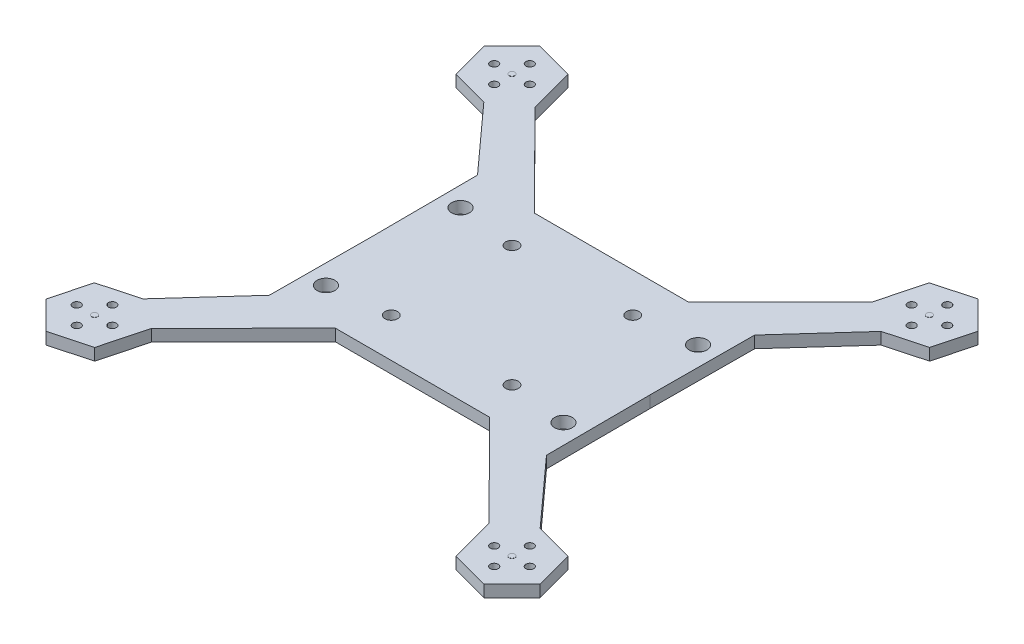
SolidWorks part; units mm, degrees
material "T700G"
ref_plane "Front Plane" through (0, 0, 0) normal (0, 0, 1) x (1, 0, 0)
ref_plane "Top Plane" through (0, 0, 0) normal (0, 1, 0) x (1, 0, 0)
ref_plane "Right Plane" through (0, 0, 0) normal (1, 0, 0) x (0, 0, -1)
sketch "Sketch1" plane through (0, 0, 0) normal (0, 1, 0) x (1, 0, 0)
  line L5 (-35, -35) -> (42.6186, 42.6186) construction
  line L6 (-35, 35) -> (35, -35) construction
  line L9 (0, 0) -> (42.4264, 42.4264) construction
  line L10 (52.7307, 48.2307) -> (52.7307, 57.2307) construction
  line L11 (30, 17) -> (30, 0) construction
  line L12 (0, 0) -> (0, 23.6863) construction
  line L28 (0, 0) -> (-174.2372, 0) construction
  line L41 (31.9599, 25.1581) -> (-25.1581, 25.1581) construction
  line L70 (42.6186, 48.4021) -> (19.4638, 25.1581)
  line L72 (48.2307, 52.7307) -> (57.2307, 52.7307) construction
  line L74 (48.2307, 52.7307) -> (52.7307, 48.2307) construction
  line L75 (55.3003, 62.3949) -> (45.646, 59.7881)
  line L77 (45.646, 59.7881) -> (42.6186, 48.4021)
  line L80 (50.185, 43.0729) -> (59.8153, 45.6732)
  line L83 (59.8153, 45.6732) -> (62.3849, 55.3374)
  line L85 (62.3849, 55.3374) -> (55.3003, 62.3949)
  line L87 (50.185, 43.0729) -> (35, 26.2883)
  line L88 (35, 26.2883) -> (34.873, 0)
  line L89 (34.873, -11.873) -> (34.873, 11.873) construction
  line L90 (-21.8355, 25.1581) -> (21.8355, 25.1581)
  line L94 (35, -26.2883) -> (34.873, 0)
  line L100 (48.2307, -52.7307) -> (52.7307, -48.2307) construction
  line L101 (48.2307, -52.7307) -> (57.2307, -52.7307) construction
  line L102 (52.7307, -48.2307) -> (52.7307, -57.2307) construction
  line L106 (62.3849, -55.3374) -> (55.3003, -62.3949)
  line L111 (59.8153, -45.6732) -> (62.3849, -55.3374)
  line L115 (50.185, -43.0729) -> (59.8153, -45.6732)
  line L116 (45.646, -59.7881) -> (42.6186, -48.4021)
  line L119 (55.3003, -62.3949) -> (45.646, -59.7881)
  line L127 (50.185, -43.0729) -> (35, -26.2883)
  line L128 (35, 26.2883) -> (34.873, 0)
  line L129 (35, -26.2883) -> (34.873, 0)
  line L135 (42.6186, -48.4021) -> (19.4638, -25.1581)
  line L138 (40.4517, 52.7386) -> (49.1512, 44.0725) [skipped]
  line L139 (-21.8355, -25.1581) -> (21.8355, -25.1581)
  line L140 (-48.2307, 52.7307) -> (-52.7307, 48.2307) construction
  line L141 (-48.2307, 52.7307) -> (-57.2307, 52.7307) construction
  line L142 (-52.7307, 48.2307) -> (-52.7307, 57.2307) construction
  line L143 (-62.3849, 55.3374) -> (-55.3003, 62.3949)
  line L144 (-59.8153, 45.6732) -> (-62.3849, 55.3374)
  line L145 (-50.185, 43.0729) -> (-59.8153, 45.6732)
  line L146 (-45.646, 59.7881) -> (-42.6186, 48.4021)
  line L147 (-55.3003, 62.3949) -> (-45.646, 59.7881)
  line L148 (-50.185, 43.0729) -> (-35, 26.2883)
  line L149 (-42.6186, 48.4021) -> (-19.4638, 25.1581)
  line L150 (-35, 26.2883) -> (-34.873, 0)
  line L151 (-35, -26.2883) -> (-34.873, 0)
  line L152 (-50.185, -43.0729) -> (-35, -26.2883)
  line L153 (-42.6186, -48.4021) -> (-19.4638, -25.1581)
  line L154 (-52.7307, -48.2307) -> (-52.7307, -57.2307) construction
  line L155 (-48.2307, -52.7307) -> (-57.2307, -52.7307) construction
  line L156 (-48.2307, -52.7307) -> (-52.7307, -48.2307) construction
  line L157 (-55.3003, -62.3949) -> (-45.646, -59.7881)
  line L158 (-45.646, -59.7881) -> (-42.6186, -48.4021)
  line L159 (-50.185, -43.0729) -> (-59.8153, -45.6732)
  line L160 (-59.8153, -45.6732) -> (-62.3849, -55.3374)
  line L161 (-62.3849, -55.3374) -> (-55.3003, -62.3949)
  circle A0 centre (-15.25, 15.25) radius 1.6
  circle A1 centre (15.25, 15.25) radius 1.6
  circle A2 centre (15.25, -15.25) radius 1.6
  circle A3 centre (-15.25, -15.25) radius 1.6
  circle A18 centre (30, 17) radius 2.25
  circle A19 centre (30, -17) radius 2.25
  circle A20 centre (-30, -17) radius 2.25
  circle A21 centre (-30, 17) radius 2.25
  circle A69 centre (52.7307, 52.7307) radius 8.6603 construction
  circle A70 centre (52.7307, 57.2307) radius 1
  circle A71 centre (52.7307, 48.2307) radius 1
  circle A72 centre (48.2307, 52.7307) radius 1
  circle A73 centre (57.2307, 52.7307) radius 1
  circle A124 centre (52.7307, -52.7307) radius 8.6603 construction
  circle A125 centre (57.2307, -52.7307) radius 1
  circle A126 centre (48.2307, -52.7307) radius 1
  circle A127 centre (52.7307, -48.2307) radius 1
  circle A128 centre (52.7307, -57.2307) radius 1
  circle A129 centre (-52.7307, 52.7307) radius 8.6603 construction
  circle A130 centre (-57.2307, 52.7307) radius 1
  circle A131 centre (-48.2307, 52.7307) radius 1
  circle A132 centre (-52.7307, 48.2307) radius 1
  circle A133 centre (-52.7307, 57.2307) radius 1
  circle A134 centre (-52.7307, -52.7307) radius 8.6603 construction
  circle A135 centre (-52.7307, -57.2307) radius 1
  circle A136 centre (-52.7307, -48.2307) radius 1
  circle A137 centre (-48.2307, -52.7307) radius 1
  circle A138 centre (-57.2307, -52.7307) radius 1
  point P0 (0, 0)
  point P8 (52.7307, 52.7307)
  point P9 (52.7307, 52.7307)
  point P17 (0, 0)
  point P45 (24.8566, 0)
  point P47 (30, 0)
  point P90 (0, 25.1581)
  point P95 (0, -25.1581)
  point P96 (0, 25.1581)
  point P99 (0, 25.1581)
  point P110 (0, -25.1581)
  point P118 (0, 0)
  point P126 (0, -25.1581)
  dimension "D3" = 3.2
  dimension "D16" = 4.5
  dimension "D1" = 70
  dimension "D2" = 4.5
  dimension "D4" = 30.5
  dimension "D6" = 4.5
  dimension "D7" = 20
  dimension "D15" = 17
  dimension "D12" = 30
  dimension "D5" = 4
  dimension "D17" = 2
extrude "Boss-Extrude1" add sketch "Sketch1" along normal blind 3 contours L144 A21 A0 A1 A2 A3 region at (0, 0, 0)
sketch "Sketch4" plane through (0, 0, 0) normal (0, -1, 0) x (1, 0, 0)
  circle A0 centre (0, 0) radius 4.9
  circle A1 centre (0, 0) radius 6.495
  dimension "D1" = 9.8
extrude "Boss-Extrude3" add sketch "Sketch4" along normal blind 5
sketch "Sketch6" plane through (0, 0, 25.1581) normal (0, 0, 1) x (1, 0, 0)
  line L0 (-6.495, 0) -> (6.495, 0) construction
  line L1 (-4.2416, -1.8916) -> (4.2416, -1.8916)
  line L2 (-4.2416, -1.8916) -> (-4.2416, 0)
  line L3 (-4.2416, 0) -> (4.2416, 0)
  line L4 (4.2416, -1.8916) -> (4.2416, 0)
  line L5 (-4.2416, -1.8916) -> (4.2416, 0) construction
  line L6 (-4.2416, 0) -> (4.2416, -1.8916) construction
  point P0 (0, -0.9458)
extrude "Cut-Extrude3" cut sketch "Sketch6" against normal blind 34
sketch "Sketch7" plane through (0, 3, 0) normal (0, 1, 0) x (1, 0, 0)
  line L0 (-57.2307, -52.7307) -> (-48.2307, -52.7307) construction
  line L1 (-52.7307, -57.2307) -> (-52.7307, -48.2307) construction
  line L2 (0, 0) -> (-75.1546, 0) construction
  line L3 (0, 0) -> (0, 55.538) construction
  circle A0 centre (-52.7307, -52.7307) radius 0.75
  circle A1 centre (-52.7307, 52.7307) radius 0.75
  circle A2 centre (52.7307, 52.7307) radius 0.75
  circle A3 centre (52.7307, -52.7307) radius 0.75
  dimension "D1" = 1.5
extrude "Boss-Extrude4" add sketch "Sketch7" along normal blind 0.05
